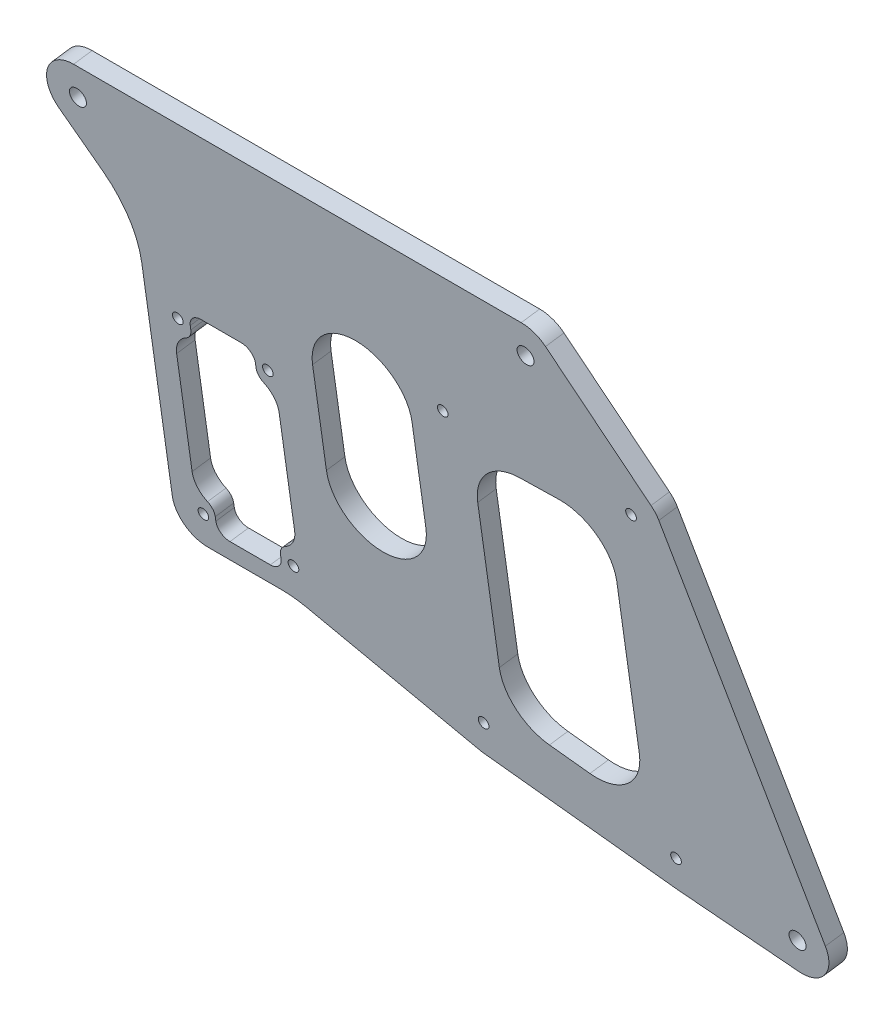
SolidWorks part; units mm, degrees
material "Acrylic (Medium-high impact)"
ref_plane "Front Plane" through (0, 0, 0) normal (0, 0, 1) x (1, 0, 0)
ref_plane "Top Plane" through (0, 0, 0) normal (0, 1, 0) x (1, 0, 0)
ref_plane "Right Plane" through (0, 0, 0) normal (1, 0, 0) x (0, 0, -1)
sketch "Sketch2" plane through (0, -851.6064, 6059.4947) normal (0, 0.1392, -0.9903) x (-1, 0, 0)
  line L1 (-291.6598, -2420.9907) -> (-107.4887, -2420.9907)
  line L2 (-291.6598, -2420.9907) -> (-291.6598, -2293.9907)
  line L3 (-291.6598, -2293.9907) -> (-107.4887, -2293.9907)
  line L4 (-107.4887, -2420.9907) -> (-107.4887, -2293.9907)
  circle A0 centre (-283.7223, -2413.0532) radius 2.1526 construction
  circle A1 centre (-115.4262, -2301.9282) radius 2.1526 construction
  dimension "D3" = 7.9375
  dimension "D2" = 7.9375
  dimension "D1" = 127
  dimension "D4" = 7.9375
extrude "Boss-Extrude1" add sketch "Sketch2" along normal blind 4.7625
hole_wizard "CSK for #6 Flat Head Machine Screw (100)1" positions "Sketch3" profile "Sketch4" countersink size "#6" standard "ANSI Inch" end condition through all
sketch "Sketch3" plane through (0, -850.9436, 6054.7786) normal (0, 0.1392, -0.9903) x (-1, 0, 0)
  circle A0 centre (-115.4262, -2301.9282) radius 2.1526 construction
  circle A1 centre (-229.7262, -2301.9282) radius 2.1527 construction
  circle A2 centre (-283.7223, -2413.0532) radius 2.1526 construction
  point P0 (-115.4262, -2301.9282)
  point P2 (-229.7262, -2301.9282)
  point P4 (-283.7223, -2413.0532)
sketch "Sketch4" plane through (115.4262, -3130.4697, 5734.4121) normal (1, 0, 0) x (0, 0.9903, 0.1392)
  line L0 (0, 0) -> (0, 22.2655)
  line L1 (0, 22.2655) -> (2.1526, 22.2655)
  line L2 (2.1526, 22.2655) -> (2.1526, 1.1669)
  line L3 (2.1526, 1.1669) -> (3.5433, 0)
  line L5 (3.5433, 0) -> (0, 0)
  line L6 (-2.1526, 1.1669) -> (-3.5433, 0) construction
  line L11 (0, -6.35) -> (0, 107.95) construction
  dimension "Thru Hole Dia." = 4.3053
  dimension "Thru Hole Depth" = 22.2655
  dimension "Near C'Sink Dia." = 7.0866
  dimension "Near C'Sink Angle" = 100
sketch "Sketch5" plane through (0, -850.9436, 6054.7786) normal (0, 0.1392, -0.9903) x (-1, 0, 0)
  line L0 (-183.275, -2361.6107) -> (-183.275, -2336.2107) construction
  line L1 (-195.975, -2361.6107) -> (-195.975, -2336.2107)
  line L2 (-170.575, -2361.6107) -> (-170.575, -2336.2107)
  line L3 (-190.775, -2361.6107) -> (-175.775, -2361.6107) construction
  arc A0 (-195.975, -2361.6107) -> (-170.575, -2361.6107) centre (-183.275, -2361.6107) ccw
  arc A1 (-170.575, -2336.2107) -> (-195.975, -2336.2107) centre (-183.275, -2336.2107) ccw
  point P2 (-183.275, -2348.9107)
  point P12 (-183.275, -2361.6107)
  dimension "D2" = 12.7
  dimension "D1" = 25.4
extrude "Cut-Extrude1" cut sketch "Sketch5" against normal through all
hole_wizard "#2 Clearance Hole1" positions "Sketch6" profile "Sketch7" hole size "#2" standard "ANSI Inch" end condition through all
sketch "Sketch6" plane through (0, -850.9436, 6054.7786) normal (0, 0.1392, -0.9903) x (-1, 0, 0)
  circle A0 centre (-135.015, -2391.3927) radius 1.6 construction
  circle A1 centre (-158.015, -2391.3927) radius 1.6 construction
  circle A2 centre (-135.015, -2344.3927) radius 1.6 construction
  circle A3 centre (-158.015, -2344.3927) radius 1.6 construction
  circle A4 centre (-204.8641, -2403.6053) radius 1.524 construction
  circle A5 centre (-253.1241, -2409.9553) radius 1.524 construction
  circle A6 centre (-253.1241, -2327.4053) radius 1.524 construction
  circle A7 centre (-204.8641, -2328.6753) radius 1.524 construction
  point P0 (-135.015, -2391.3927)
  point P3 (-158.015, -2391.3927)
  point P6 (-158.015, -2344.3927)
  point P9 (-135.015, -2344.3927)
  point P12 (-204.8641, -2328.6753)
  point P15 (-204.8641, -2403.6053)
  point P18 (-253.1241, -2409.9553)
  point P21 (-253.1241, -2327.4053)
  point P24 (0, 0)
  point P27 (0, 0)
  point P30 (0, 0)
  point P33 (0, 0)
  point P36 (0, 0)
  point P39 (0, 0)
  point P42 (0, 0)
  point P45 (0, 0)
sketch "Sketch7" plane through (135.015, -3219.0635, 5721.961) normal (1, 0, 0) x (0, 0.9903, 0.1392)
  line L0 (0, 0) -> (0, 22.2655)
  line L1 (0, 22.2655) -> (1.3525, 22.2655)
  line L2 (1.3525, 22.2655) -> (1.3525, 0)
  line L5 (1.3525, 0) -> (0, 0)
  line L11 (0, -6.35) -> (0, 107.95) construction
  dimension "Thru Hole Dia." = 2.7051
  dimension "Thru Hole Depth" = 22.2655
sketch "Sketch9" plane through (0, -850.9436, 6054.7786) normal (0, 0.1392, -0.9903) x (-1, 0, 0)
  line L0 (-291.6598, -2293.9907) -> (-291.6598, -2420.9907) construction
  line L1 (-107.4887, -2293.9907) -> (-291.6598, -2293.9907) construction
  line L2 (-107.4887, -2420.9907) -> (-107.4887, -2293.9907) construction
  line L3 (-282.9228, -2420.9504) -> (-252.3246, -2417.8525)
  line L4 (-203.8286, -2411.475) -> (-252.0886, -2417.825)
  line L5 (-156.9974, -2399.3302) -> (-202.8619, -2411.2861)
  line L6 (-135.015, -2399.3302) -> (-156.9974, -2399.3302)
  line L7 (-127.0775, -2391.3927) -> (-127.0775, -2324.8049)
  line L8 (-127.0775, -2324.8049) -> (-109.8135, -2307.5409)
  line L9 (-115.4262, -2293.9907) -> (-229.7262, -2293.9907)
  line L10 (-258.9702, -2322.0363) -> (-235.5723, -2296.5592)
  line L11 (-260.5989, -2324.7349) -> (-291.1971, -2410.3828)
  line L16 (-291.6598, -2293.9907) -> (-291.6598, -2420.9907)
  line L17 (-291.6598, -2420.9907) -> (-107.4887, -2420.9907)
  line L18 (-107.4887, -2420.9907) -> (-107.4887, -2293.9907)
  line L19 (-107.4887, -2293.9907) -> (-291.6598, -2293.9907)
  line L20 (-291.6598, -2293.9907) -> (-291.6598, -2420.9907)
  line L21 (-291.6598, -2420.9907) -> (-107.4887, -2420.9907)
  line L22 (-107.4887, -2420.9907) -> (-107.4887, -2293.9907)
  line L23 (-107.4887, -2293.9907) -> (-291.6598, -2293.9907)
  circle A0 centre (-229.7262, -2301.9282) radius 7.9375 construction
  circle A1 centre (-115.4262, -2301.9282) radius 7.9375 construction
  circle A2 centre (-283.7223, -2413.0532) radius 7.9375 construction
  circle A3 centre (-253.1241, -2327.4053) radius 7.9375 construction
  circle A4 centre (-253.1241, -2409.9553) radius 7.9375 construction
  circle A5 centre (-204.8641, -2403.6053) radius 7.9375 construction
  arc A6 (-252.0886, -2417.825) -> (-252.3246, -2417.8525) centre (-253.1241, -2409.9553) cw
  circle A7 centre (-158.015, -2391.3927) radius 7.9375 construction
  circle A8 centre (-135.015, -2391.3927) radius 7.9375 construction
  arc A9 (-202.8619, -2411.2861) -> (-203.8286, -2411.475) centre (-204.8641, -2403.6053) cw
  arc A10 (-109.8135, -2307.5409) -> (-115.4262, -2293.9907) centre (-115.4262, -2301.9282) ccw
  arc A11 (-282.9228, -2420.9504) -> (-291.1971, -2410.3828) centre (-283.7223, -2413.0532) cw
  arc A12 (-260.5989, -2324.7349) -> (-258.9702, -2322.0363) centre (-253.1241, -2327.4053) cw
  arc A13 (-229.7262, -2293.9907) -> (-235.5723, -2296.5592) centre (-229.7262, -2301.9282) ccw
  arc A14 (-135.015, -2399.3302) -> (-127.0775, -2391.3927) centre (-135.015, -2391.3927) ccw
  line M19 (-291.6598, -2293.9907) -> (-291.6598, -2420.9907)
  line M20 (-291.6598, -2420.9907) -> (-107.4887, -2420.9907)
  line M21 (-107.4887, -2420.9907) -> (-107.4887, -2293.9907)
  line M22 (-107.4887, -2293.9907) -> (-291.6598, -2293.9907)
  dimension "D1" = 15.875
  dimension "D2" = 135
  dimension "D3" = 0
extrude "Cut-Extrude2" cut sketch "Sketch9" against normal blind 4.7625 contours A14 L6 L5 A9 L4 A6 L3 A11 L21 A10 L8 L7 M21 | A13 A11 L11 A12 L10 M22 M19 | A10 L22 M22 | A11 L20 M20 region at (267.6022, -3247.0091, 5718.0335) region at (289.8868, -3246.6177, 5718.0885) region at (274.9686, -3158.8592, 5730.4222) region at (109.2617, -3124.3651, 5735.27)
fillet "Fillet1" radius 25.4 2 edges at (127.0775, -3153.4551, 5733.5863) (156.9974, -3227.2551, 5723.2144)
sketch "Sketch10" plane through (0, -850.9436, 6054.7786) normal (0, 0.1392, -0.9903) x (-1, 0, 0)
  line L1 (-133.4275, -2388.2177) -> (-138.19, -2388.2177)
  line L2 (-133.4275, -2388.2177) -> (-133.4275, -2347.5677)
  line L3 (-133.4275, -2347.5677) -> (-138.19, -2347.5677)
  line L4 (-159.6025, -2388.2177) -> (-159.6025, -2347.5677)
  line L6 (-154.84, -2388.2177) -> (-159.6025, -2388.2177)
  line L8 (-138.19, -2388.2177) -> (-138.19, -2394.5677)
  line L9 (-138.19, -2394.5677) -> (-154.84, -2394.5677)
  line L10 (-154.84, -2388.2177) -> (-154.84, -2394.5677)
  line L11 (-154.84, -2347.5677) -> (-159.6025, -2347.5677)
  line L13 (-138.19, -2347.5677) -> (-138.19, -2341.2177)
  line L14 (-138.19, -2341.2177) -> (-154.84, -2341.2177)
  line L15 (-154.84, -2347.5677) -> (-154.84, -2341.2177)
  circle A0 centre (-135.015, -2344.3927) radius 1.3526 construction
  circle A1 centre (-135.015, -2344.3927) radius 1.3526 construction
  circle A3 centre (-135.015, -2391.3927) radius 1.3526 construction
  circle A4 centre (-158.015, -2391.3927) radius 1.3526 construction
  circle A5 centre (-158.015, -2344.3927) radius 1.3526 construction
  dimension "D2" = 3.175
  dimension "D1" = 1.5875
  dimension "D3" = 3.175
  dimension "D4" = 1.5875
  dimension "D5" = 3.175
  dimension "D6" = 3.175
  dimension "D7" = 3.175
  dimension "D8" = 3.175
extrude "Cut-Extrude3" cut sketch "Sketch10" against normal through all
fillet "Fillet2" radius 6.35 4 edges at (133.4275, -3175.9964, 5730.4184) (133.4275, -3216.2508, 5724.761) (159.6025, -3175.9964, 5730.4184) (159.6025, -3216.2508, 5724.761)
sketch "Sketch11" plane through (0, -850.9436, 6054.7786) normal (0, 0.1392, -0.9903) x (-1, 0, 0)
  line L0 (-253.1241, -2409.9553) -> (-204.8641, -2403.6053) construction
  line L1 (-204.8641, -2403.6053) -> (-204.8641, -2328.6753) construction
  line L2 (-204.8641, -2328.6753) -> (-253.1241, -2327.4053) construction
  line L3 (-253.1241, -2327.4053) -> (-253.1241, -2409.9553) construction
  line L4 (-246.7741, -2333.9246) -> (-246.7741, -2402.7151)
  line L5 (-246.7741, -2402.7151) -> (-211.2141, -2398.0361)
  line L6 (-211.2141, -2398.0361) -> (-211.2141, -2334.8604)
  line L7 (-211.2141, -2334.8604) -> (-246.7741, -2333.9246)
  circle A0 centre (-253.1241, -2409.9553) radius 7.9375 construction
  circle A1 centre (-204.8641, -2403.6053) radius 7.9375 construction
  circle A2 centre (-253.1241, -2327.4053) radius 7.9375 construction
  circle A3 centre (-204.8641, -2328.6753) radius 7.9375 construction
  dimension "D1" = 15.875
  dimension "D2" = 6.35
extrude "Cut-Extrude4" cut sketch "Sketch11" against normal through all
fillet "Fillet3" radius 12.7 4 edges at (211.2141, -3163.4128, 5732.1869) (246.7741, -3162.4861, 5732.3171) (211.2141, -3225.9736, 5723.3945) (246.7741, -3230.607, 5722.7433)
fillet "Fillet4" radius 3.175 8 edges at (138.19, -3169.7082, 5731.3021) (154.84, -3169.7082, 5731.3021) (154.84, -3222.539, 5723.8772) (138.19, -3222.539, 5723.8772) (138.19, -3216.2508, 5724.761) (138.19, -3175.9964, 5730.4184) (154.84, -3216.2508, 5724.761) (154.84, -3175.9964, 5730.4184)
